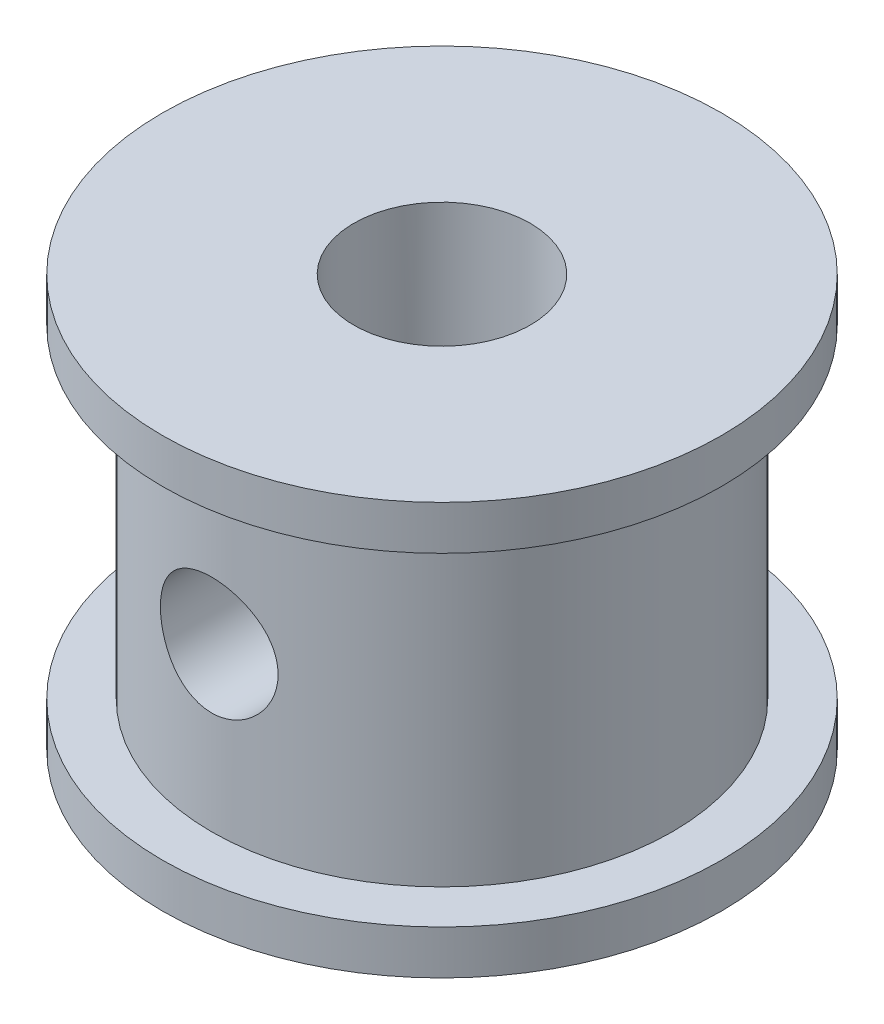
SolidWorks part; units mm, degrees
ref_plane "Front Plane" through (0, 0, 0) normal (0, 0, 1) x (1, 0, 0)
ref_plane "Top Plane" through (0, 0, 0) normal (0, 1, 0) x (1, 0, 0)
ref_plane "Right Plane" through (0, 0, 0) normal (1, 0, 0) x (0, 0, -1)
sketch "草圖1" plane through (0, 0, 0) normal (0, 1, 0) x (1, 0, 0)
  circle A0 centre (0, 0) radius 7.83
  dimension "D1" = 15.66
extrude "填料-伸長1" add sketch "草圖1" along normal blind 5.5 and the other way blind 5.5
sketch "草圖3" plane through (0, -5.5, 0) normal (0, -1, 0) x (1, 0, 0)
  circle A0 centre (0, 0) radius 9.5
  dimension "D1" = 19
extrude "填料-伸長3" add sketch "草圖3" along normal blind 1.5
sketch "草圖4" plane through (0, 5.5, 0) normal (0, 1, 0) x (1, 0, 0)
  circle A0 centre (0, 0) radius 9.5
  dimension "D1" = 19
extrude "填料-伸長4" add sketch "草圖4" along normal blind 1.5
sketch "草圖5" plane through (0, -7, 0) normal (0, -1, 0) x (1, 0, 0)
  circle A0 centre (0, 0) radius 3
  dimension "D1" = 6
extrude "除料-伸長1" cut sketch "草圖5" against normal through all
sketch "草圖6" plane through (0, 0, 0) normal (0, 0, 1) x (1, 0, 0)
  circle A0 centre (0, 0) radius 2
  dimension "D1" = 4
extrude "除料-伸長2" cut sketch "草圖6" along normal through all
sketch "草圖7" plane through (0, 0, 0) normal (1, 0, 0) x (0, 0, -1)
  circle A0 centre (0, 0) radius 2
  dimension "D1" = 4
extrude "除料-伸長3" cut sketch "草圖7" against normal through all
